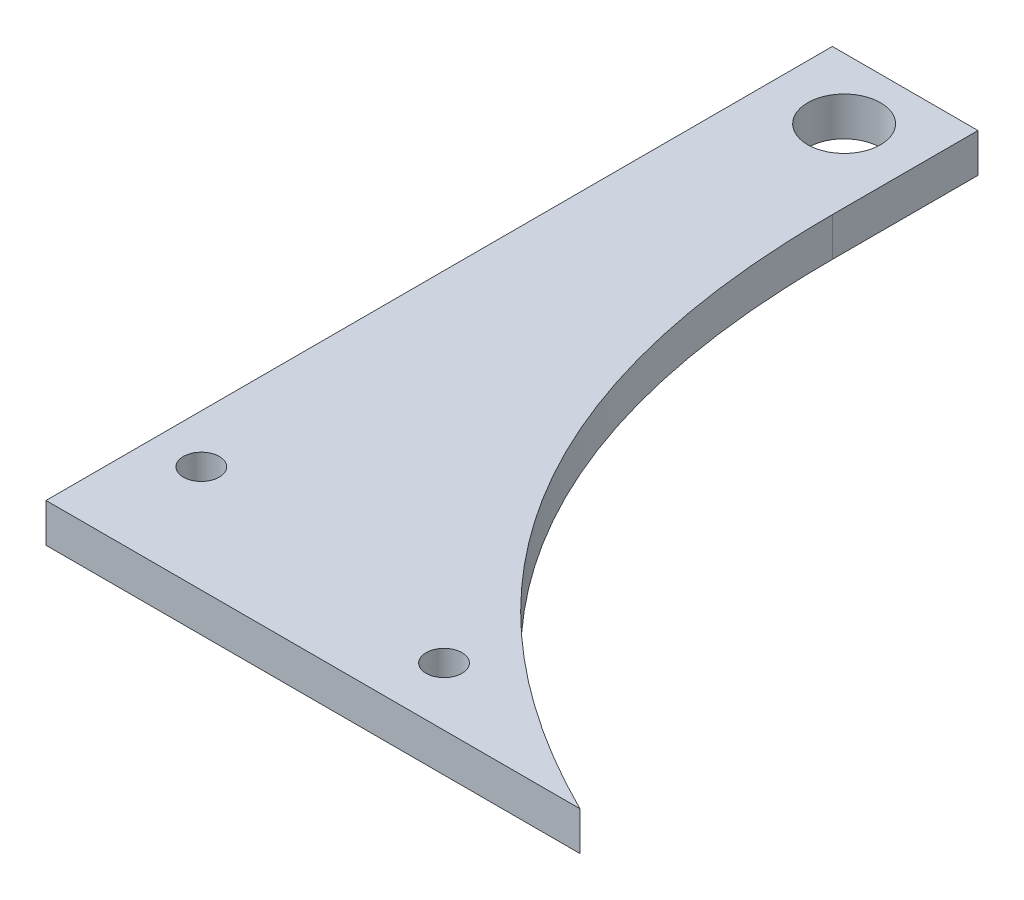
SolidWorks part; units mm, degrees
ref_plane "Front Plane" through (0, 0, 0) normal (0, 0, 1) x (1, 0, 0)
ref_plane "Top Plane" through (0, 0, 0) normal (0, 1, 0) x (1, 0, 0)
ref_plane "Right Plane" through (0, 0, 0) normal (1, 0, 0) x (0, 0, -1)
sketch "Sketch1" plane through (0, 0, 0) normal (0, 1, 0) x (1, 0, 0)
  line L0 (9.525, -53.975) -> (60.325, -53.975) construction
  line L1 (-9.525, -53.975) -> (9.525, -53.975) construction
  line L2 (-9.525, -53.975) -> (-9.525, 53.975) construction
  line L3 (-9.525, 53.975) -> (9.525, 53.975)
  line L4 (9.525, -53.975) -> (9.525, 53.975) construction
  line L5 (-9.525, -53.975) -> (9.525, 53.975) construction
  line L6 (-9.525, 53.975) -> (9.525, -53.975) construction
  line L7 (0, 53.975) -> (0, 45.9867) construction
  line L8 (-9.525, 50.7492) -> (9.525, 50.7492) construction
  line L9 (9.525, 34.925) -> (9.525, 53.975)
  line L10 (60.325, -53.975) -> (60.325, -48.895) construction
  line L11 (60.325, -48.895) -> (-9.525, -48.895) construction
  line L12 (60.325, -53.975) -> (60.325, -48.895) construction
  line L13 (60.325, -48.895) -> (-9.525, -48.895)
  line L14 (-9.525, -48.895) -> (-9.525, 53.975)
  circle A0 centre (0, 45.9867) radius 4.7625
  spline S0 degree 2 poles (60.325, -48.895) (9.525, -23.6383) (9.525, 34.925) knots 0 0 0 1 1 1
  point P4 (0, 0)
  dimension "D5" = 9.525
  dimension "D1" = 107.95
  dimension "D2" = 19.05
  dimension "D3" = 50.8
  dimension "D4" = 19.05
  dimension "D6" = 104.7242
  dimension "D7" = 5.08
extrude "Boss-Extrude1" add sketch "Sketch1" along normal blind 5.08
sketch "Sketch3" plane through (0, 5.08, 0) normal (0, 1, 0) x (1, 0, 0)
  circle A1 centre (-3.175, -34.925) radius 3.175 construction
  circle A3 centre (34.925, -41.275) radius 3.175 construction
  circle A4 centre (34.925, -41.275) radius 2.3495
  circle A5 centre (-3.175, -34.925) radius 2.3495
  dimension "D1" = 4.699
  dimension "D2" = 4.699
extrude "Cut-Extrude1" cut sketch "Sketch3" against normal through all
